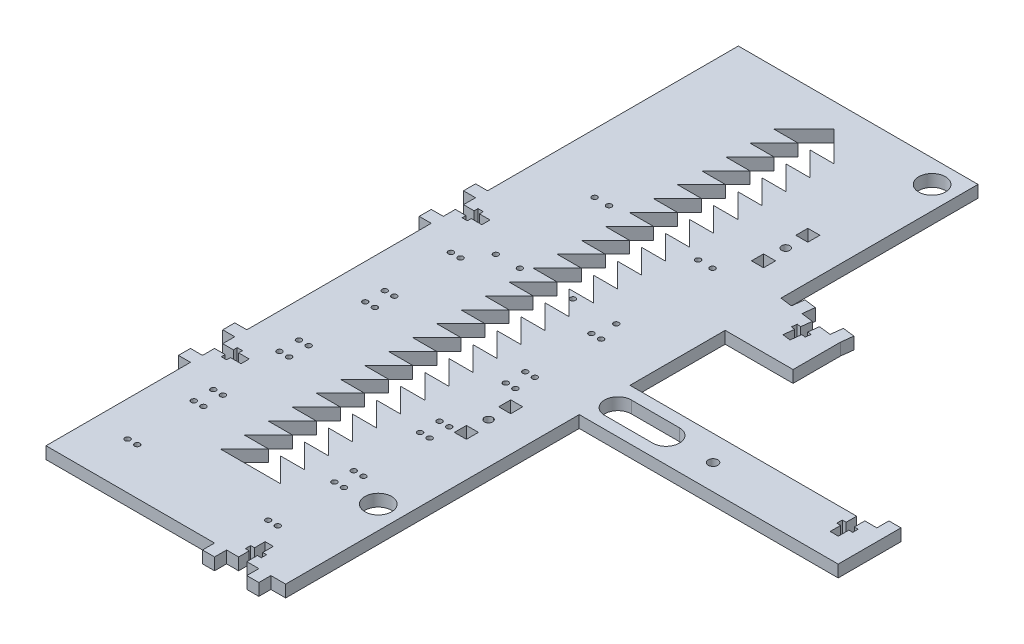
SolidWorks part; units mm, degrees
ref_plane "Front Plane" through (0, 0, 0) normal (0, 0, 1) x (1, 0, 0)
ref_plane "Top Plane" through (0, 0, 0) normal (0, 1, 0) x (1, 0, 0)
ref_plane "Right Plane" through (0, 0, 0) normal (1, 0, 0) x (0, 0, -1)
sketch "Axle Support Plate" plane through (0, 0, 0) normal (0, 1, 0) x (1, 0, 0)
  line L0 (51.0949, 170.4749) -> (51.0949, -121.6251) construction
  line L1 (38.3949, 182.5851) -> (38.3949, -110.9142) construction
  line L2 (0, 169.8851) -> (-15.875, 154.0101)
  line L3 (-15.875, 154.0101) -> (-3.175, 154.0101)
  line L4 (63.2051, -182.5851) -> (63.2051, -102.2391)
  line L5 (-63.2051, 182.5851) -> (63.2051, -182.5851) construction
  line L6 (-63.2051, -182.5851) -> (63.2051, 182.5851) construction
  line L7 (-63.2051, -76.6671) -> (-63.2051, 20.6149)
  line L8 (-63.2051, 182.5851) -> (63.2051, 182.5851)
  line L9 (0, 182.5851) -> (0, -182.5851) construction
  line L10 (15.875, 154.0101) -> (0, 169.8851)
  line L11 (-3.175, 154.0101) -> (-15.875, 141.3101)
  line L12 (-15.875, 141.3101) -> (-3.175, 141.3101)
  line L13 (15.875, 141.3101) -> (3.175, 154.0101)
  line L14 (-3.175, 141.3101) -> (-15.875, 128.6101)
  line L15 (-15.875, 128.6101) -> (-3.175, 128.6101)
  line L16 (15.875, 128.6101) -> (3.175, 141.3101)
  line L17 (63.2051, 24.4249) -> (8.4551, 24.4249) construction
  line L18 (-3.175, 128.6101) -> (-15.875, 115.9101)
  line L19 (-15.875, 115.9101) -> (-3.175, 115.9101)
  line L20 (15.875, 115.9101) -> (3.175, 128.6101)
  line L21 (-3.175, 115.9101) -> (-15.875, 103.2101)
  line L22 (-15.875, 103.2101) -> (-3.175, 103.2101)
  line L23 (55.4129, -182.5851) -> (63.2051, -182.5851)
  line L24 (15.875, 103.2101) -> (3.175, 115.9101)
  line L25 (-3.175, 103.2101) -> (-15.875, 90.5101)
  line L26 (-15.875, 90.5101) -> (-3.175, 90.5101)
  line L27 (15.875, 90.5101) -> (3.175, 103.2101)
  line L28 (-3.175, 90.5101) -> (-15.875, 77.8101)
  line L29 (-15.875, 77.8101) -> (-3.175, 77.8101)
  line L30 (15.875, 77.8101) -> (3.175, 90.5101)
  line L31 (-3.175, 77.8101) -> (-15.875, 65.1101)
  line L32 (-15.875, 65.1101) -> (-3.175, 65.1101)
  line L33 (15.875, 65.1101) -> (3.175, 77.8101)
  line L34 (-3.175, 65.1101) -> (-15.875, 52.4101)
  line L35 (-15.875, 52.4101) -> (-3.175, 52.4101)
  line L36 (15.875, 52.4101) -> (3.175, 65.1101)
  line L37 (63.2051, -0.9751) -> (182.7572, -0.9751)
  line L38 (171.8352, -0.9751) -> (171.8352, -27.7353) construction
  line L39 (199.7752, -27.7353) -> (63.2051, -27.7353)
  line L40 (70.2352, -14.3552) -> (95.6352, -14.3552) construction
  line L41 (70.2352, -7.3251) -> (95.6352, -7.3251)
  line L42 (70.2352, -21.3853) -> (95.6352, -21.3853)
  line L43 (63.2051, -14.3552) -> (199.7752, -14.3552) construction
  line L44 (187.0752, -0.9751) -> (193.4252, -0.9751)
  line L46 (63.2051, -0.9751) -> (63.2051, 182.5851)
  line L47 (63.2051, -0.9751) -> (63.2051, -27.7353) construction
  line L49 (-3.175, 52.4101) -> (-15.875, 39.7101)
  line L50 (-15.875, 39.7101) -> (-3.175, 39.7101)
  line L51 (199.7752, -0.9751) -> (199.7752, -27.7353)
  line L52 (15.875, 39.7101) -> (3.175, 52.4101)
  line L53 (-3.175, 39.7101) -> (-15.875, 27.0101)
  line L54 (-15.875, 27.0101) -> (-3.175, 27.0101)
  line L55 (15.875, 27.0101) -> (3.175, 39.7101)
  line L56 (-3.175, 27.0101) -> (-15.875, 14.3101)
  line L57 (-15.875, 14.3101) -> (-3.175, 14.3101)
  line L58 (15.875, 14.3101) -> (3.175, 27.0101)
  line L59 (3.175, 1.6101) -> (15.875, 1.6101)
  line L60 (-15.875, 1.6101) -> (-3.175, 1.6101)
  line L61 (15.875, 1.6101) -> (3.175, 14.3101)
  line L62 (-3.175, 1.6101) -> (-15.875, -11.0899)
  line L63 (-15.875, -11.0899) -> (-3.175, -11.0899)
  line L64 (15.875, -11.0899) -> (3.175, 1.6101)
  line L65 (-3.175, -11.0899) -> (-15.875, -23.7899)
  line L66 (-15.875, -23.7899) -> (-3.175, -23.7899)
  line L67 (15.875, -23.7899) -> (3.175, -11.0899)
  line L68 (-3.175, -23.7899) -> (-15.875, -36.4899)
  line L69 (-15.875, -36.4899) -> (-3.175, -36.4899)
  line L70 (15.875, -36.4899) -> (3.175, -23.7899)
  line L71 (-3.175, -36.4899) -> (-15.875, -49.1899)
  line L72 (-15.875, -49.1899) -> (-3.175, -49.1899)
  line L73 (15.875, -49.1899) -> (3.175, -36.4899)
  line L74 (-3.175, -49.1899) -> (-15.875, -61.8899)
  line L75 (-15.875, -61.8899) -> (-3.175, -61.8899)
  line L76 (15.875, -61.8899) -> (3.175, -49.1899)
  line L77 (-3.175, -61.8899) -> (-15.875, -74.5899)
  line L78 (-15.875, -74.5899) -> (-3.175, -74.5899)
  line L79 (15.875, -74.5899) -> (3.175, -61.8899)
  line L80 (-3.175, -74.5899) -> (-15.875, -87.2899)
  line L81 (-63.2051, 50.3329) -> (-63.2051, 182.5851)
  line L82 (-15.875, -87.2899) -> (-3.175, -87.2899)
  line L83 (15.875, -87.2899) -> (3.175, -74.5899)
  line L84 (-3.175, -87.2899) -> (-15.875, -99.9899)
  line L85 (-15.875, -99.9899) -> (-3.175, -99.9899)
  line L86 (15.875, -99.9899) -> (3.175, -87.2899)
  line L87 (-3.175, -99.9899) -> (-15.875, -112.6899)
  line L88 (-15.875, -112.6899) -> (-3.175, -112.6899)
  line L89 (15.875, -112.6899) -> (3.175, -99.9899)
  line L90 (25.6949, -182.5851) -> (-63.2051, -182.5851)
  line L91 (-3.175, -112.6899) -> (-15.875, -125.3899)
  line L92 (-15.875, -125.3899) -> (-3.175, -125.3899)
  line L93 (15.875, -125.3899) -> (3.175, -112.6899)
  line L94 (-63.2051, -182.5851) -> (-63.2051, -106.3851)
  line L95 (-3.175, -125.3899) -> (-15.875, -138.0899)
  line L96 (-15.875, -138.0899) -> (15.875, -138.0899)
  line L97 (15.875, -138.0899) -> (3.175, -125.3899)
  line L98 (3.175, 154.0101) -> (15.875, 154.0101)
  line L99 (3.175, 128.6101) -> (15.875, 128.6101)
  line L100 (3.175, 141.3101) -> (15.875, 141.3101)
  line L101 (3.175, 115.9101) -> (15.875, 115.9101)
  line L102 (3.175, 90.5101) -> (15.875, 90.5101)
  line L103 (3.175, 103.2101) -> (15.875, 103.2101)
  line L104 (3.175, 77.8101) -> (15.875, 77.8101)
  line L105 (3.175, 65.1101) -> (15.875, 65.1101)
  line L106 (3.175, 52.4101) -> (15.875, 52.4101)
  line L107 (3.175, 39.7101) -> (15.875, 39.7101)
  line L108 (3.175, 27.0101) -> (15.875, 27.0101)
  line L109 (3.175, 14.3101) -> (15.875, 14.3101)
  line L110 (-3.175, 14.3101) -> (-15.875, 1.6101)
  line L111 (-6.5087, 10.9763) -> (-7.7272, 9.7579) [skipped]
  line L112 (3.175, -11.0899) -> (15.875, -11.0899)
  line L113 (3.175, -23.7899) -> (15.875, -23.7899)
  line L114 (3.175, -36.4899) -> (15.875, -36.4899)
  line L115 (3.175, -49.1899) -> (15.875, -49.1899)
  line L116 (3.175, -61.8899) -> (15.875, -61.8899)
  line L117 (3.175, -74.5899) -> (15.875, -74.5899)
  line L118 (3.175, -87.2899) -> (15.875, -87.2899)
  line L119 (3.175, -99.9899) -> (15.875, -99.9899)
  line L120 (3.175, -112.6899) -> (15.875, -112.6899)
  line L121 (3.175, -125.3899) -> (15.875, -125.3899)
  line L125 (63.2051, -102.2391) -> (63.2051, -27.7353)
  line L126 (-63.5861, -218.1451) -> (63.5861, -218.1451) construction
  circle A0 centre (51.0949, 170.4749) radius 7.0301
  circle A1 centre (51.0949, -121.6251) radius 7.0301
  circle A2 centre (51.0949, -121.6251) radius 12.7 construction
  circle A3 centre (120.4002, -14.3552) radius 2.54
  arc A4 (70.2352, -7.3251) -> (70.2352, -21.3853) centre (70.2352, -14.3552) ccw
  arc A5 (95.6352, -21.3853) -> (95.6352, -7.3251) centre (95.6352, -14.3552) ccw
  circle A6 centre (95.6352, -14.3552) radius 15.875 construction
  point P8 (0, 0)
  point P15 (51.0949, 24.4249)
  point P57 (82.9352, -14.3552)
  point P144 (63.7949, -121.6251)
  point P145 (51.0949, -134.3251)
  point P146 (111.5102, -14.3552)
  point P147 (117.8602, -14.3552)
  line B0 (-63.2051, -83.0171) -> (-69.5551, -83.0171)
  line B1 (-69.5551, -83.0171) -> (-69.5551, -76.6671)
  line B2 (-69.5551, -76.6671) -> (-63.2051, -76.6671)
  line B3 (-63.2051, -89.3671) -> (-57.6171, -89.3671)
  line B4 (-57.6171, -89.3671) -> (-57.6171, -87.3261)
  line B5 (-57.6171, -87.3261) -> (-54.8231, -87.3261)
  line B6 (-54.8231, -87.3261) -> (-54.8231, -89.3671)
  line B7 (-54.8231, -89.3671) -> (-49.2351, -89.3671)
  line B8 (-49.2351, -89.3671) -> (-49.2351, -93.6851)
  line B9 (-49.2351, -93.6851) -> (-54.8231, -93.6851)
  line B10 (-54.8231, -93.6851) -> (-54.8231, -95.7261)
  line B11 (-54.8231, -95.7261) -> (-57.6171, -95.7261)
  line B12 (-57.6171, -95.7261) -> (-57.6171, -93.6851)
  line B13 (-57.6171, -93.6851) -> (-63.2051, -93.6851)
  line B14 (-49.2351, -91.5261) -> (-63.2051, -91.5261) construction
  line B15 (-63.2051, -100.0351) -> (-63.2051, -93.6851)
  line B16 (-69.5551, -106.3851) -> (-63.2051, -106.3851)
  line B17 (-63.2051, -83.0171) -> (-63.2051, -89.3671)
  line B18 (-69.5551, -100.0351) -> (-69.5551, -106.3851)
  line B19 (-63.2051, -100.0351) -> (-69.5551, -100.0351)
  line B20 (-63.2051, 43.9829) -> (-69.5551, 43.9829)
  line B21 (-69.5551, 43.9829) -> (-69.5551, 50.3329)
  line B22 (-69.5551, 50.3329) -> (-63.2051, 50.3329)
  line B23 (-63.2051, 37.6329) -> (-57.6171, 37.6329)
  line B24 (-57.6171, 37.6329) -> (-57.6171, 39.6739)
  line B25 (-57.6171, 39.6739) -> (-54.8231, 39.6739)
  line B26 (-54.8231, 39.6739) -> (-54.8231, 37.6329)
  line B27 (-54.8231, 37.6329) -> (-49.2351, 37.6329)
  line B28 (-49.2351, 37.6329) -> (-49.2351, 33.3149)
  line B29 (-49.2351, 33.3149) -> (-54.8231, 33.3149)
  line B30 (-54.8231, 33.3149) -> (-54.8231, 31.2739)
  line B31 (-54.8231, 31.2739) -> (-57.6171, 31.2739)
  line B32 (-57.6171, 31.2739) -> (-57.6171, 33.3149)
  line B33 (-57.6171, 33.3149) -> (-63.2051, 33.3149)
  line B34 (-49.2351, 35.4739) -> (-63.2051, 35.4739) construction
  line B35 (-63.2051, 26.9649) -> (-63.2051, 33.3149)
  line B36 (-69.5551, 20.6149) -> (-63.2051, 20.6149)
  line B37 (-63.2051, 43.9829) -> (-63.2051, 37.6329)
  line B38 (-69.5551, 26.9649) -> (-69.5551, 20.6149)
  line B39 (-63.2051, 26.9649) -> (-69.5551, 26.9649)
  line B40 (32.0449, -182.5851) -> (32.0449, -188.9351)
  line B41 (32.0449, -188.9351) -> (25.6949, -188.9351)
  line B42 (25.6949, -188.9351) -> (25.6949, -182.5851)
  line B43 (38.3949, -182.5851) -> (38.3949, -176.9971)
  line B44 (38.3949, -176.9971) -> (36.3539, -176.9971)
  line B45 (36.3539, -176.9971) -> (36.3539, -174.2031)
  line B46 (36.3539, -174.2031) -> (38.3949, -174.2031)
  line B47 (38.3949, -174.2031) -> (38.3949, -168.6151)
  line B48 (38.3949, -168.6151) -> (42.7129, -168.6151)
  line B49 (42.7129, -168.6151) -> (42.7129, -174.2031)
  line B50 (42.7129, -174.2031) -> (44.7539, -174.2031)
  line B51 (44.7539, -174.2031) -> (44.7539, -176.9971)
  line B52 (44.7539, -176.9971) -> (42.7129, -176.9971)
  line B53 (42.7129, -176.9971) -> (42.7129, -182.5851)
  line B54 (40.5539, -168.6151) -> (40.5539, -182.5851) construction
  line B55 (49.0629, -182.5851) -> (42.7129, -182.5851)
  line B56 (55.4129, -188.9351) -> (55.4129, -182.5851)
  line B57 (32.0449, -182.5851) -> (38.3949, -182.5851)
  line B58 (49.0629, -188.9351) -> (55.4129, -188.9351)
  line B59 (49.0629, -182.5851) -> (49.0629, -188.9351)
  line B60 (41.5699, 87.9249) -> (41.5699, 117.6429) construction
  line B61 (39.4109, 102.7839) -> (43.7289, 102.7839) construction
  line B62 (38.3949, 111.2929) -> (44.7449, 111.2929)
  line B63 (38.3949, 111.2929) -> (38.3949, 117.6429)
  line B64 (38.3949, 117.6429) -> (44.7449, 117.6429)
  line B65 (44.7449, 111.2929) -> (44.7449, 117.6429)
  line B66 (38.3949, 111.2929) -> (44.7449, 117.6429) construction
  line B67 (38.3949, 117.6429) -> (44.7449, 111.2929) construction
  line B68 (38.3949, 87.9249) -> (44.7449, 94.2749) construction
  line B69 (38.3949, 94.2749) -> (44.7449, 87.9249) construction
  line B70 (44.7449, 94.2749) -> (44.7449, 87.9249)
  line B71 (38.3949, 87.9249) -> (44.7449, 87.9249)
  line B72 (38.3949, 94.2749) -> (38.3949, 87.9249)
  line B73 (38.3949, 94.2749) -> (44.7449, 94.2749)
  circle B74 centre (41.5699, 102.7839) radius 2.159
  line B75 (41.5699, -39.0751) -> (41.5699, -68.7931) construction
  line B76 (39.4109, -53.9341) -> (43.7289, -53.9341) construction
  line B77 (38.3949, -62.4431) -> (44.7449, -62.4431)
  line B78 (38.3949, -62.4431) -> (38.3949, -68.7931)
  line B79 (38.3949, -68.7931) -> (44.7449, -68.7931)
  line B80 (44.7449, -62.4431) -> (44.7449, -68.7931)
  line B81 (38.3949, -62.4431) -> (44.7449, -68.7931) construction
  line B82 (38.3949, -68.7931) -> (44.7449, -62.4431) construction
  line B83 (38.3949, -39.0751) -> (44.7449, -45.4251) construction
  line B84 (38.3949, -45.4251) -> (44.7449, -39.0751) construction
  line B85 (44.7449, -45.4251) -> (44.7449, -39.0751)
  line B86 (38.3949, -39.0751) -> (44.7449, -39.0751)
  line B87 (38.3949, -45.4251) -> (38.3949, -39.0751)
  line B88 (38.3949, -45.4251) -> (44.7449, -45.4251)
  circle B89 centre (41.5699, -53.9341) radius 2.159
  line B90 (187.0752, -0.9751) -> (187.0752, -6.5101)
  line B91 (187.0752, -6.5101) -> (189.1162, -6.5101)
  line B92 (189.1162, -6.5101) -> (189.1162, -9.4101)
  line B93 (189.1162, -9.4101) -> (187.0752, -9.4101)
  line B94 (187.0752, -9.4101) -> (187.0752, -14.9451)
  line B95 (187.0752, -14.9451) -> (182.7572, -14.9451)
  line B96 (182.7572, -14.9451) -> (182.7572, -9.4101)
  line B97 (182.7572, -9.4101) -> (180.7162, -9.4101)
  line B98 (180.7162, -9.4101) -> (180.7162, -6.5101)
  line B99 (180.7162, -6.5101) -> (182.7572, -6.5101)
  line B100 (182.7572, -6.5101) -> (182.7572, -0.9751)
  line B101 (193.4252, -0.9751) -> (193.4252, 5.3749)
  line B102 (193.4252, 5.3749) -> (199.7752, 5.3749)
  line B103 (199.7752, 5.3749) -> (199.7752, -0.9751)
  dimension "D1" = 5.08
  dimension "D4" = 14.0603
  dimension "D5" = 5.08
  dimension "D8" = 31.75
  dimension "D14" = 14.0603
  dimension "D15" = 5.08
  dimension "D16" = 31.75
  dimension "D22" = 7.0301
  dimension "D25" = 6.35
  dimension "D13" = 25.4
  dimension "D19" = 83.82
  dimension "D21" = 76.2
  dimension "D2" = 292.1
  dimension "D6" = 12.7
  dimension "D7" = 63.5
  dimension "D9" = 88.9
  dimension "D10" = 12.7
  dimension "D11" = 24
  dimension "D12" = 10.541
  dimension "D17" = 6.35
  dimension "D18" = 35.56
  dimension "D20" = 27.94
  dimension "D23" = 6.35
  dimension "D24" = 25.4
  dimension "D26" = 25.4
  dimension "D27" = 6.35
  dimension "D28" = 60.96
  dimension "D29" = 76.2
  dimension "D30" = 203.2
sketch_block_instance "Male T-slot assembly-1"
sketch_block "Male T-slot assembly" parameters "D1"=6.35, "D2"=6.35, "D3"=4.318, "D4"=2.794, "D5"=8.4, "D6"=13.97, "D7"=6.35
sketch_block_instance "Male T-slot assembly-2"
sketch_block_instance "Male T-slot assembly-4"
sketch_block_instance "Female T-Slot Assembly-1"
sketch_block "Female T-Slot Assembly" parameters "D4"=4.318, "D1"=6.35, "D2"=6.35, "D3"=6.35
sketch_block_instance "Female T-Slot Assembly-3"
sketch_block_instance "Block-T-Slot_2-1"
sketch_block "Block-T-Slot_2" parameters "D1"=4.318, "D2"=2.9, "D3"=8.4, "D4"=13.97
sketch_block_instance "Block-T-slot_Tab-3"
sketch_block "Block-T-slot_Tab" parameters "D1"=6.35, "D2"=6.35
extrude "Boss-Extrude1" add sketch "Axle Support Plate" along normal blind 6.35 contours L23 L4 L39 L51 L37 L46 L8 region at (9.407, 0, 3.1626)
sketch "Sketch1" plane through (0, 6.35, 0) normal (0, 1, 0) x (1, 0, 0)
  line L0 (63.2051, -0.9751) -> (63.2051, 182.5851) construction
  line L1 (99.0042, 74.2572) -> (99.0042, 49.2391)
  line L2 (99.0042, 49.2391) -> (63.2051, 49.2391)
  line L3 (44.0648, 170.4749) -> (58.1251, 170.4749) construction
  line L4 (51.0949, 177.5051) -> (51.0949, 163.4448) construction
  line L5 (69.5077, 77.8789) -> (63.2051, 78.6528)
  line L6 (63.2051, 78.6528) -> (63.2051, 49.2391)
  line L7 (-63.2051, 182.5851) -> (63.2051, 182.5851) construction
  line L8 (63.2051, 78.6528) -> (63.9789, 84.9555) construction
  line L9 (-63.2051, 53.8889) -> (63.2051, 53.8889) construction
  line L10 (-63.2051, 50.3329) -> (-63.2051, 182.5851) construction
  line L11 (55.4129, -182.5851) -> (63.2051, -182.5851) construction
  line L12 (99.0042, 74.2572) -> (264.8904, 53.8889) construction
  line L13 (63.2051, 53.8889) -> (264.8904, 53.8889) construction
  circle A0 centre (51.0949, 170.4749) radius 7.0301 construction
  point P12 (51.0949, 170.4749)
  point P21 (59.309, -182.5851)
  line B0 (92.7016, 75.0311) -> (93.4754, 81.3337)
  line B1 (93.4754, 81.3337) -> (99.7781, 80.5599)
  line B2 (99.7781, 80.5599) -> (99.0042, 74.2572)
  line B3 (86.3989, 75.8049) -> (85.7179, 70.2586)
  line B4 (85.7179, 70.2586) -> (87.7437, 70.0099)
  line B5 (87.7437, 70.0099) -> (87.4032, 67.2367)
  line B6 (87.4032, 67.2367) -> (85.3774, 67.4854)
  line B7 (85.3774, 67.4854) -> (84.6964, 61.9391)
  line B8 (84.6964, 61.9391) -> (80.4106, 62.4653)
  line B9 (80.4106, 62.4653) -> (81.0916, 68.0117)
  line B10 (81.0916, 68.0117) -> (79.0658, 68.2604)
  line B11 (79.0658, 68.2604) -> (79.4063, 71.0336)
  line B12 (79.4063, 71.0336) -> (81.4321, 70.7848)
  line B13 (81.4321, 70.7848) -> (82.1131, 76.3312)
  line B14 (82.5535, 62.2022) -> (84.256, 76.0681) construction
  line B15 (75.8104, 77.105) -> (82.1131, 76.3312)
  line B16 (70.2816, 84.1816) -> (69.5077, 77.8789)
  line B17 (92.7016, 75.0311) -> (86.3989, 75.8049)
  line B18 (76.5843, 83.4077) -> (70.2816, 84.1816)
  line B19 (75.8104, 77.105) -> (76.5843, 83.4077)
  dimension "D1" = 7
  dimension "D2" = 12.7
  dimension "D3" = 203.2
  dimension "D4" = 6.35
  dimension "D5" = 236.474
  dimension "D6" = 97.6296
sketch_block_instance "Male T-slot assembly-9"
extrude "Boss-Extrude2" add sketch "Sketch1" against normal blind 6.35 contours B15 B19 B18 B16 L6 L2 L1 B2 B1 B0 B17 B3 B4 B5 B6 B7 B8 B9 B10 B11 B12 B13 region at (98.4984, 6.35, -61.7481)
sketch "Sketch2" plane through (0, 6.35, 0) normal (0, 1, 0) x (1, 0, 0)
  line L0 (0, 169.8851) -> (0, -138.0899) construction
  line L1 (-15.875, -138.0899) -> (15.875, -138.0899) construction
  line L2 (-19.2844, 23.4639) -> (23.8956, 23.4639) construction
  line L3 (23.8956, 23.4639) -> (23.8956, 75.6609) construction
  line L4 (-19.2844, 23.4639) -> (-24.3644, 23.4639) construction
  line L5 (-24.3644, 23.4639) -> (-24.3644, 76.9309) construction
  line L6 (-24.3644, 75.5339) -> (23.8956, 75.5339) construction
  circle A0 centre (51.0949, 170.4749) radius 15.875 construction
  circle A1 centre (8.6556, 23.4639) radius 1.397
  circle A2 centre (-19.2844, 23.4639) radius 1.397
  circle A3 centre (23.8956, 74.2639) radius 1.397
  circle A4 centre (-24.3644, 75.5339) radius 1.397
  circle A5 centre (-31.9844, 75.5339) radius 1.397
  circle A6 centre (31.5156, 74.2639) radius 1.397
  circle A7 centre (-31.9844, 23.4639) radius 1.397
  circle A8 centre (31.5156, 23.4639) radius 1.397
  circle B0 centre (-39.6583, -123.1085) radius 1.397
  circle B1 centre (34.4779, -123.1085) radius 1.397
  circle B2 centre (29.3979, -123.1085) radius 1.397
  circle B3 centre (-44.7383, -158.0335) radius 1.397
  circle B4 centre (-44.7383, -123.1085) radius 1.397
  circle B5 centre (29.3979, -158.0335) radius 1.397
  circle B6 centre (-39.6583, -158.0335) radius 1.397
  circle B7 centre (34.4779, -158.0335) radius 1.397
  circle B8 centre (-39.6583, -77.9027) radius 1.397
  circle B9 centre (34.4779, -77.9027) radius 1.397
  line B10 (29.3979, -77.9027) -> (29.3979, -112.8277) construction
  line B11 (-5.1302, -77.9027) -> (-5.1302, -95.3652) construction
  circle B12 centre (29.3979, -77.9027) radius 1.397
  circle B13 centre (-44.7383, -112.8277) radius 1.397
  circle B14 centre (-44.7383, -77.9027) radius 1.397
  circle B15 centre (29.3979, -112.8277) radius 1.397
  circle B16 centre (-39.6583, -112.8277) radius 1.397
  circle B17 centre (34.4779, -112.8277) radius 1.397
  circle B18 centre (-39.6583, -32.6968) radius 1.397
  circle B19 centre (34.4779, -32.6968) radius 1.397
  line B20 (29.3979, -50.1593) -> (-39.6583, -50.1593) construction
  circle B21 centre (29.3979, -32.6968) radius 1.397
  circle B22 centre (-44.7383, -67.6218) radius 1.397
  circle B23 centre (-44.7383, -32.6968) radius 1.397
  circle B24 centre (29.3979, -67.6218) radius 1.397
  circle B25 centre (-39.6583, -67.6218) radius 1.397
  circle B26 centre (34.4779, -67.6218) radius 1.397
  circle B27 centre (-39.6583, 12.509) radius 1.397
  circle B28 centre (34.4779, 12.509) radius 1.397
  circle B29 centre (29.3979, 12.509) radius 1.397
  circle B30 centre (-44.7383, -22.416) radius 1.397
  circle B31 centre (-44.7383, 12.509) radius 1.397
  circle B32 centre (29.3979, -22.416) radius 1.397
  circle B33 centre (-39.6583, -22.416) radius 1.397
  circle B34 centre (34.4779, -22.416) radius 1.397
  dimension "D1" = 31.75
  dimension "D2" = 4
  dimension "D3" = 2.794
  dimension "D9" = 7.62
  dimension "D4" = 27.94
  dimension "D5" = 15.24
  dimension "D6" = 50.8
  dimension "D7" = 5.08
  dimension "D8" = 1.27
  dimension "D10" = 7.62
sketch_block_instance "Block1-1"
sketch_block "Block1" parameters "D1"=2.3813, "D2"=2.794, "D3"=69.0563, "D4"=69.0563
sketch_block_instance "Block1-4"
sketch_block_instance "Block1-5"
sketch_block_instance "Block1-6"
extrude "Cut-Extrude1" cut sketch "Sketch2" against normal blind 6.35
equation "\"Ball Diameter\"= 1.75in"
equation "\"Sheet Thickness\"= 0.25in"
equation "\"Screw Diameter\"= .17in"
equation "\"Robot Diameter\"= 14in"
equation "\"Castor Screw Diameter\"= 0.22in"
equation "\"Wheel Diameter\" = 4in"
equation "\"Nut Diameter\" = 8.4mm"
equation "\"Nut Height\" = 2.9mm"
equation "\"Screw Height\" = 0.55in"
equation "\"Pulley Diameter\" = 1in"
equation "\"Reactor Height\" = 14in"
equation "\"Elevator Height\" = 11.5in"
equation "\"Elevator Width\" = \"Ball Diameter\" + 0.25in"
equation "\"D1@Boss-Extrude1\"=\"Sheet Thickness\""
equation "\"Elevator Bearing Diameter\" = sqr(2*(\"Sheet Thickness\"^2)) + 0.2in"
equation "\"Elevator Axle Length\" = \"Elevator Width\" + 8*\"Sheet Thickness\""
equation "\"D13@Axle Support Plate\"=\"Pulley Diameter\""
equation "\"D9@Axle Support Plate\"=\"Elevator Clearance from Axis\""
equation "\"D14@Axle Support Plate\" = \"Elevator Bearing Diameter\""
equation "\"D22@Axle Support Plate\"=\"Elevator Bearing Diameter\"/2"
equation "\"D23@Axle Support Plate\" = \"Sheet Thickness\""
equation "\"Elevator Axle Endcap Diameter\" = \"Pulley Diameter\" + 0.25in"
equation "\"D27@Axle Support Plate\"=\"Sheet Thickness\""
equation "\"Elevator Clearance from Axis\" = 3.5in"
equation "\"D3@Sketch1\"=\"Length of Chute\""
equation "\"Ball Radius\" = \"Ball Diameter\"/2"
equation "\"Elevator Horizontal Clearance\" = \"Elevator Width\" + 0.5in"
equation "\"Claw Horizontal Seperation\" = (\"Elevator Width\"/2) - (1.5 * \"Sheet Thickness\") - 0.15in"
equation "\"Claw Radius\" = \"Ball Radius\" + 0.1in"
equation "\"Castor Wheel Height\" = 1.25in"
equation "\"Length of Chute\" = 8in"
equation "\"D16@Axle Support Plate\"=\"Elevator Axle Endcap Diameter\""
